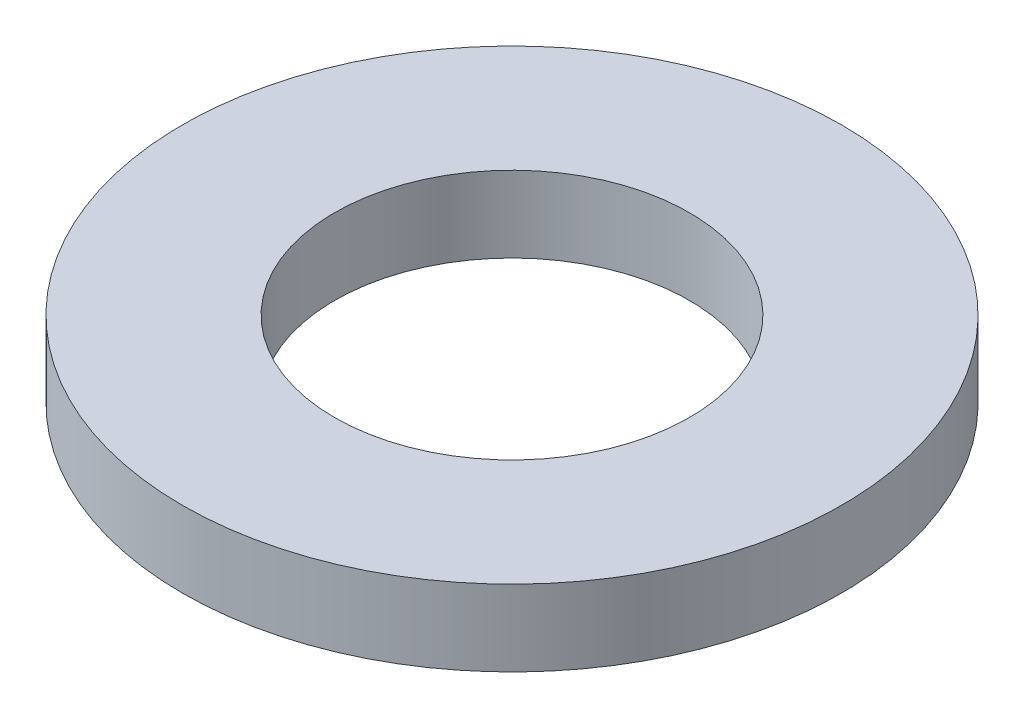
SolidWorks part; units mm, degrees
ref_plane "Front Plane" through (0, 0, 0) normal (0, 0, 1) x (1, 0, 0)
ref_plane "Top Plane" through (0, 0, 0) normal (0, 1, 0) x (1, 0, 0)
ref_plane "Right Plane" through (0, 0, 0) normal (1, 0, 0) x (0, 0, -1)
sketch "Sketch1" plane through (0, 0, 0) normal (0, 1, 0) x (1, 0, 0)
  circle A0 centre (0, 0) radius 3.5
  circle A1 centre (0, 0) radius 6.5
  dimension "D1" = 7
  dimension "D2" = 3
extrude "Boss-Extrude1" add sketch "Sketch1" along normal blind 1.5
